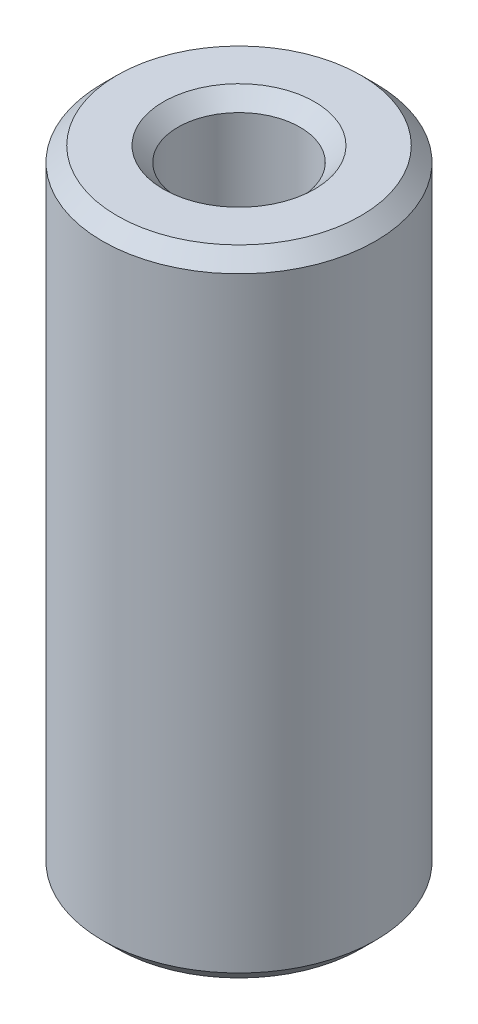
SolidWorks part; units mm, degrees
ref_plane "Front Plane" through (0, 0, 0) normal (0, 0, 1) x (1, 0, 0)
ref_plane "Top Plane" through (0, 0, 0) normal (0, 1, 0) x (1, 0, 0)
ref_plane "Right Plane" through (0, 0, 0) normal (1, 0, 0) x (0, 0, -1)
sketch "Sketch1" plane through (0, 0, 0) normal (0, 1, 0) x (1, 0, 0)
  circle A0 centre (0, 0) radius 12.5
  dimension "SLEEVE_OD" = 25
extrude "Boss-Extrude1" add sketch "Sketch1" along normal blind 58.1393
sketch "Sketch2" plane through (0, 0, 0) normal (0, 1, 0) x (1, 0, 0)
  circle A0 centre (0, 0) radius 5.5901
  dimension "BORE_D" = 11.1801
extrude "Cut-Extrude1" cut sketch "Sketch2" along normal through all
chamfer "Chamfer1" distance 1.3417 angle 45 4 edges at (0, 58.1393, 5.5901) (0, 0, 5.5901) (0, 0, 12.5) (0, 58.1393, 12.5)
